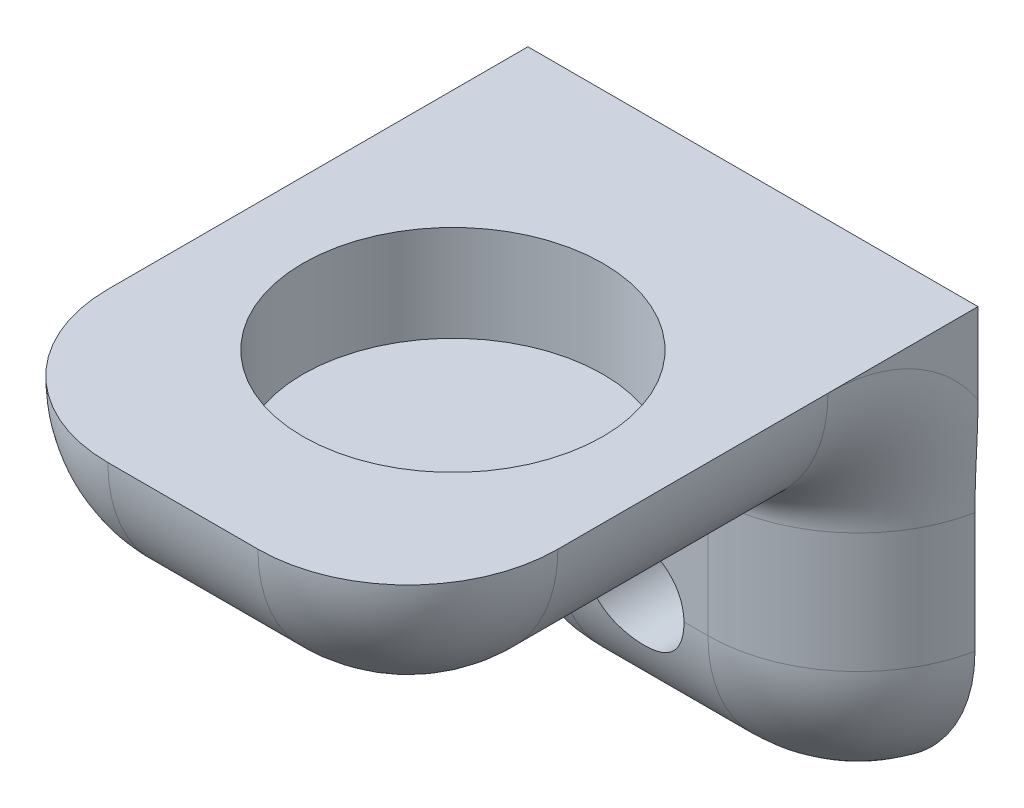
SolidWorks part; units mm, degrees
ref_plane "Front Plane" through (0, 0, 0) normal (0, 0, 1) x (1, 0, 0)
ref_plane "Top Plane" through (0, 0, 0) normal (0, 1, 0) x (1, 0, 0)
ref_plane "Right Plane" through (0, 0, 0) normal (1, 0, 0) x (0, 0, -1)
sketch "Sketch1" plane through (0, 0, 0) normal (0, 1, 0) x (1, 0, 0)
  line L1 (0, 0) -> (15, 0)
  line L2 (0, 0) -> (0, 4)
  line L3 (0, 4) -> (15, 4)
  line L4 (15, 0) -> (15, 4)
  dimension "D1" = 4
  dimension "D2" = 15
extrude "Boss-Extrude1" add sketch "Sketch1" along normal blind 15
sketch "Sketch2" plane through (0, 0, 0) normal (0, 0, 1) x (1, 0, 0)
  line L0 (15, 15) -> (15, 0) construction
  line L1 (0, 15) -> (15, 15)
  line L2 (0, 15) -> (0, 10)
  line L3 (0, 10) -> (15, 10)
  line L4 (15, 15) -> (15, 10)
  dimension "D1" = 5
extrude "Boss-Extrude2" add sketch "Sketch2" along normal blind 15
fillet "Fillet1" radius 1 1 edges at (7.5, 10, 0)
fillet "Fillet3" radius 5 7 edges at (0, 4.5, 0) (0, 9.7071, 0.2929) (15, 4.5, 0) (15, 9.7071, 0.2929) (0, 10, 8) (15, 10, 8) (7.5, 10, 15)
sketch "Sketch3" plane through (0, 15, 0) normal (0, 1, 0) x (1, 0, 0)
  line L0 (15, 4) -> (0, 4) construction
  line L1 (0, 4) -> (0, -1) construction
  circle A0 centre (7.5, -6) radius 5
  dimension "D1" = 10
  dimension "D2" = 10
  dimension "D3" = 7.5
extrude "Cut-Extrude1" cut sketch "Sketch3" against normal blind 3.2
sketch "Sketch4" plane through (0, 0, 0) normal (0, 0, 1) x (1, 0, 0)
  line L1 (15, 15) -> (0, 15) construction
  line L2 (0.101, 0) -> (0.101, 9) construction
  circle A0 centre (7.601, 5) radius 1.6
  point P2 (0, 0)
  dimension "D1" = 3.2
  dimension "D3" = 7.5
  dimension "D2" = 10
extrude "Cut-Extrude2" cut sketch "Sketch4" against normal through all
fillet "Fillet4" radius 5 3 edges at (1.8377, 0, -1.127) (13.1623, 0, -1.127) (7.5, 0, 0)
